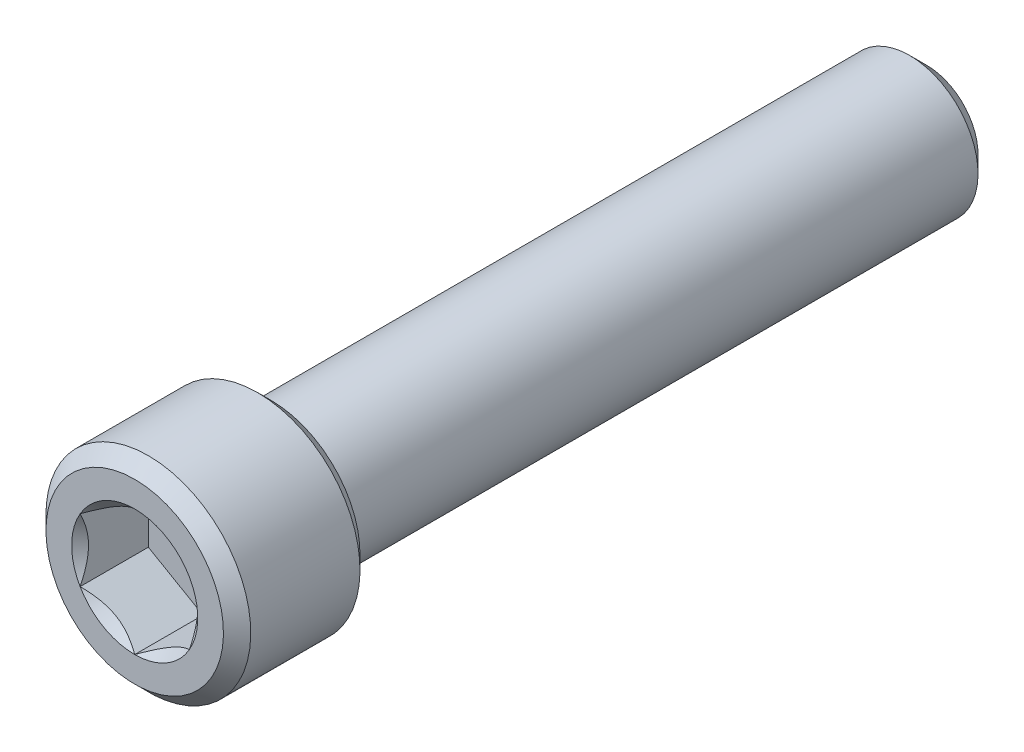
SolidWorks part; units mm, degrees
ref_plane "Front Plane" through (0, 0, 0) normal (0, 0, 1) x (1, 0, 0)
ref_plane "Top Plane" through (0, 0, 0) normal (0, 1, 0) x (1, 0, 0)
ref_plane "Right Plane" through (0, 0, 0) normal (1, 0, 0) x (0, 0, -1)
sketch "Sketch1" plane through (0, 0, 0) normal (1, 0, 0) x (0, 0, -1)
  line L0 (23.0188, 0) -> (-23.0188, 0) construction
  line L1 (-23.0188, 0) -> (-23.0188, 5.1594)
  line L2 (-23.0188, 5.1594) -> (-22.225, 5.9531)
  line L3 (-22.225, 5.9531) -> (-15.875, 5.9531)
  line L4 (-15.875, 5.9531) -> (-15.0813, 5.1594)
  line L5 (-15.0813, 5.1594) -> (-15.0813, 3.9751)
  line L6 (-15.0813, 3.9751) -> (22.031, 3.9751)
  line L7 (22.031, 3.9751) -> (23.0187, 2.9873)
  line L8 (23.0187, 2.9873) -> (23.0188, 0)
  line L9 (22.9306, 4.1279) -> (24.3417, 4.1279) construction
  line L10 (24.3417, 4.1279) -> (23.6361, 2.9058) construction
  line L11 (23.6361, 2.9058) -> (22.9306, 4.1279) construction
  line L12 (23.0188, 3.9751) -> (24.2535, 3.9751) construction
  line L13 (23.6361, 4.1279) -> (23.6361, 3.9751) construction
  line L14 (23.5479, 3.0586) -> (23.7243, 3.0586) construction
  line L15 (23.6361, 3.0586) -> (23.6361, 2.9058) construction
  line L16 (22.9747, 4.0515) -> (24.2976, 4.0515)
  line L17 (24.2976, 4.0515) -> (23.7243, 3.0586)
  line L18 (23.7243, 3.0586) -> (23.5479, 3.0586)
  line L19 (23.5479, 3.0586) -> (22.9747, 4.0515)
  line L20 (22.031, -3.9751) -> (19.491, -3.9751) construction
  point P3 (-21.8281, 5.9531)
  point P4 (0, 0)
  point P25 (23.6361, 4.0515)
  point P26 (23.0188, 3.9751)
  point P28 (-16.2719, 5.9531)
  point P29 (-19.05, 5.9531)
  point P33 (19.491, -3.9751)
  dimension "Head Ht" = 7.9375
  dimension "Screw Size" = 7.9502
  dimension "Head Dia" = 11.9062
  dimension "D1" = 45
  dimension "D2" = 45
  dimension "D3" = 0.7937
  dimension "D4" = 0.7937
  dimension "Pitch" = 1.4111
  dimension "D5" = 0.1764
  dimension "D6" = 0.9878
  dimension "D7" = 2.54
  dimension "Length" = 38.1
  dimension "D8" = 0.3969
  dimension "D9" = 0.3969
sketch "Sketch2" plane through (0, 0, 0) normal (0, 0, 1) x (1, 0, 0)
  line L0 (-0.1381, 5.9515) -> (0, 5.6555)
  line L1 (0, 3.6662) -> (-3.175, 1.8331)
  line L2 (-3.175, 1.8331) -> (-3.175, -1.8331)
  line L3 (-3.175, -1.8331) -> (0, -3.6662)
  line L4 (0, -3.6662) -> (3.175, -1.8331)
  line L5 (3.175, -1.8331) -> (3.175, 1.8331)
  line L6 (3.175, 1.8331) -> (0, 3.6662)
  line L7 (0, 5.6555) -> (0.1381, 5.9515)
  line L8 (0, -5.9531) -> (0, 5.9531) construction
  line L9 (0, 0) -> (0.1381, 5.9515) construction
  line L10 (0, 0) -> (-0.1381, 5.9515) construction
  circle A0 centre (0, 0) radius 3.175 construction
  circle A1 centre (0, 0) radius 5.9531
  circle A2 centre (0, 0) radius 5.6555 construction
  point P1 (0, 5.9531)
  point P19 (0, 0)
  dimension "D1" = 11.9062
  dimension "D3" = 11.3109
  dimension "Drive Size" = 6.35
  dimension "D2" = 2.658
sketch "Sketch3" plane through (0, 0, 0) normal (1, 0, 0) x (0, 0, -1)
  line L0 (23.0188, 0) -> (-23.0188, 0) construction
  line L1 (-23.0188, 0) -> (-23.0188, 5.1594) construction
  line L2 (-23.0188, 5.1594) -> (-22.225, 5.9531) construction
  line L3 (-22.225, 5.9531) -> (-15.875, 5.9531) construction
  line L4 (-15.875, 5.9531) -> (-15.0813, 5.1594) construction
  line L5 (-15.0813, 5.1594) -> (-15.0813, 3.9751) construction
  line L6 (-15.0813, 3.9751) -> (22.031, 3.9751) construction
  line L7 (22.031, 3.9751) -> (23.0187, 2.9873) construction
  line L8 (23.0187, 2.9873) -> (23.0188, 0) construction
  line L9 (23.0188, 0) -> (-23.0188, 0)
  line L10 (-23.0188, 0) -> (-23.0188, 5.1594)
  line L11 (-23.0188, 5.1594) -> (-22.225, 5.9531)
  line L12 (-22.225, 5.9531) -> (-15.875, 5.9531)
  line L13 (-15.875, 5.9531) -> (-15.0813, 5.1594)
  line L14 (-15.0813, 5.1594) -> (-15.0813, 3.9751)
  line L15 (-15.0813, 3.9751) -> (22.031, 3.9751)
  line L16 (22.031, 3.9751) -> (23.0187, 2.9873)
  line L17 (23.0187, 2.9873) -> (23.0188, 0)
revolve "Revolve1" add sketch "Sketch3" angle 360 about L0
sketch "Sketch4" plane through (0, 0, 23.0188) normal (0, 0, 1) x (1, 0, 0)
  line L0 (0, -3.6662) -> (3.175, -1.8331) construction
  line L1 (3.175, -1.8331) -> (3.175, 1.8331) construction
  line L2 (3.175, 1.8331) -> (0, 3.6662) construction
  line L3 (0, 3.6662) -> (-3.175, 1.8331) construction
  line L4 (-3.175, 1.8331) -> (-3.175, -1.8331) construction
  line L5 (-3.175, -1.8331) -> (0, -3.6662) construction
  line L6 (0, -3.6662) -> (3.175, -1.8331)
  line L7 (3.175, -1.8331) -> (3.175, 1.8331)
  line L8 (3.175, 1.8331) -> (0, 3.6662)
  line L9 (0, 3.6662) -> (-3.175, 1.8331)
  line L10 (-3.175, 1.8331) -> (-3.175, -1.8331)
  line L11 (-3.175, -1.8331) -> (0, -3.6662)
extrude "Cut-Extrude1" cut sketch "Sketch4" against normal blind 3.9688
sketch "Sketch5" plane through (0, 0, 23.0188) normal (0, 0, 1) x (1, 0, 0)
  circle A0 centre (0, 0) radius 3.6662
extrude "Cut-Extrude3" cut sketch "Sketch5" against normal through all draft 45
ref_axis "Center Axis1" through (0, 0, 15.0813) along (0, 0, -1)
split "Split1" [suppressed] bodies to split 107
sketch "Sketch6" [suppressed] plane through (0, 0, -23.0188) normal (0, 0, -1) x (-1, 0, 0)
  circle A0 centre (0, 0) radius 3.9751 construction
  circle A1 centre (0, 0) radius 3.9751
curve "Helix/Spiral1" [suppressed] pitch 1.4111 height 39.5111 turns 28
sketch "Sketch7" [suppressed] plane through (0, 0, 0) normal (1, 0, 0) x (0, 0, -1)
  line L0 (22.9747, 4.0515) -> (24.2976, 4.0515) construction
  line L1 (24.2976, 4.0515) -> (23.7243, 3.0586) construction
  line L2 (23.7243, 3.0586) -> (23.5479, 3.0586) construction
  line L3 (23.5479, 3.0586) -> (22.9747, 4.0515) construction
  line L4 (22.9747, 4.0515) -> (24.2976, 4.0515)
  line L5 (24.2976, 4.0515) -> (23.7243, 3.0586)
  line L6 (23.7243, 3.0586) -> (23.5479, 3.0586)
  line L7 (23.5479, 3.0586) -> (22.9747, 4.0515)
sweep "Cut-Sweep1" [suppressed] cut profiles "Sketch7" path "Helix/Spiral1"
sketch "Sketch8" [suppressed] plane through (0, 0, 15.0813) normal (0, 0, -1) x (-1, 0, 0)
  circle A0 centre (0, 0) radius 3.9751
  point P3 (0, 3.9751)
extrude "Boss-Extrude1" [suppressed] add sketch "Sketch8" along normal blind 2.54 draft 80
ref_plane "Plane1" [suppressed] through (0, 0, 19.05) normal (0, 0, 1) x (1, 0, 0)
sketch "Sketch9" [suppressed] plane through (0, 0, 19.05) normal (0, 0, 1) x (1, 0, 0)
  line L0 (-0.1381, 5.9515) -> (0, 5.6555) construction
  line L1 (0, 5.6555) -> (0.1381, 5.9515) construction
  line L2 (-0.1381, 5.9515) -> (0, 5.6555)
  line L3 (0, 5.6555) -> (0.1381, 5.9515)
  circle A0 centre (0, 0) radius 5.9531 construction
  arc A1 (0.1381, 5.9515) -> (-0.1381, 5.9515) centre (0, 0) ccw
extrude "Cut-Extrude4" [suppressed] cut sketch "Sketch9" against normal up to vertex and the other way up to vertex
pattern_circular "CirPattern1" [suppressed] count 125 over 360 about axis through (0, 0, -23.0188) along (0, 0, 1) reverse direction yes of bodies 114
equation "\"D3@Sketch1\"=\"Head Ht@Sketch1\"/10"
equation "\"D4@Sketch1\"=\"Head Ht@Sketch1\"/10"
equation "\"D5@Sketch1\"=\"Pitch@Sketch1\"/8"
equation "\"D6@Sketch1\"=\"Pitch@Sketch1\"*.7"
equation "\"D7@Sketch1\"=\"Pitch@Sketch1\"*2.5-\"D6@Sketch1\""
equation "\"D1@Cut-Extrude1\"=\"Head Ht@Sketch1\"/2"
equation "\"D4@Helix/Spiral1\"=\"Pitch@Sketch1\""
equation "\"D3@Helix/Spiral1\"=\"Length@Sketch1\"+\"D4@Helix/Spiral1\""
equation "\"D3@Sketch2\"= \"D1@Sketch2\" * .95"
equation "\"D8@Sketch1\"=\"D4@Sketch1\"/2"
equation "\"D9@Sketch1\"=\"D3@Sketch1\"/2"
equation "\"D1@CirPattern1\"=(360/\"D2@Sketch2\")-10"
